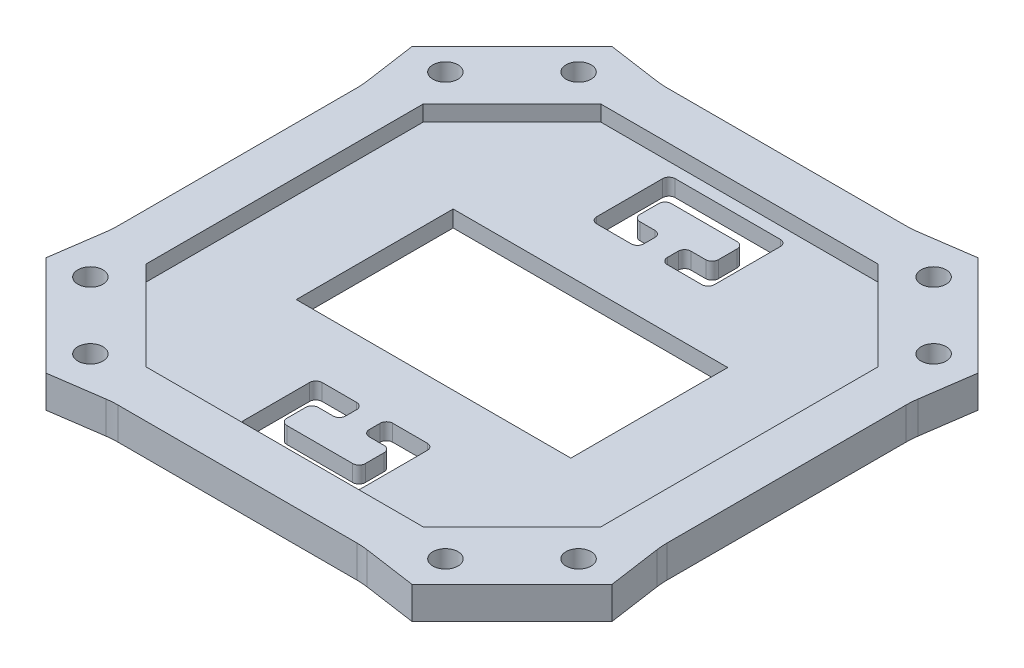
SolidWorks part; units mm, degrees
ref_plane "Front Plane" through (0, 0, 0) normal (0, 0, 1) x (1, 0, 0)
ref_plane "Top Plane" through (0, 0, 0) normal (0, 1, 0) x (1, 0, 0)
ref_plane "Right Plane" through (0, 0, 0) normal (1, 0, 0) x (0, 0, -1)
sketch "Sketch1" plane through (0, 0, 0) normal (0, 1, 0) x (1, 0, 0)
  line L0 (0, 0) -> (84.8528, 84.8528) construction
  line L5 (35, -35) -> (-35, 35) construction
  line L6 (35, 35) -> (-35, -35) construction
  line L7 (0, -62.8714) -> (0, 35) construction
  line L8 (15.934, 35) -> (-15.934, 35)
  line L9 (35, -15.934) -> (35, 15.934)
  line L10 (-15.934, -35) -> (15.934, -35)
  line L11 (-35, 15.934) -> (-35, -15.934)
  line L12 (20.5061, 33.234) -> (33.234, 20.5061) construction
  line L13 (36.0624, 23.3345) -> (23.3345, 36.0624)
  line L14 (15.934, 35) -> (23.3345, 36.0624)
  line L15 (35, 15.934) -> (36.0624, 23.3345)
  line L16 (15.934, -35) -> (23.3345, -36.0624)
  line L17 (23.3345, -36.0624) -> (36.0624, -23.3345)
  line L18 (35, -15.934) -> (36.0624, -23.3345)
  line L19 (-35, -15.934) -> (-36.0624, -23.3345)
  line L20 (-36.0624, -23.3345) -> (-23.3345, -36.0624)
  line L21 (-15.934, -35) -> (-23.3345, -36.0624)
  line L22 (-15.934, 35) -> (-23.3345, 36.0624)
  line L23 (-23.3345, 36.0624) -> (-36.0624, 23.3345)
  line L24 (-35, 15.934) -> (-36.0624, 23.3345)
  circle A0 centre (22.6274, 31.1127) radius 1.6
  circle A1 centre (31.1127, 22.6274) radius 1.6
  circle A2 centre (22.6274, -31.1127) radius 1.6
  circle A3 centre (31.1127, -22.6274) radius 1.6
  circle A4 centre (-31.1127, -22.6274) radius 1.6
  circle A5 centre (-22.6274, -31.1127) radius 1.6
  circle A6 centre (-22.6274, 31.1127) radius 1.6
  circle A7 centre (-31.1127, 22.6274) radius 1.6
  point P0 (0, 0)
  point P13 (0, 35)
  point P22 (0, 0)
  point P29 (29.6985, 29.6985)
  point P56 (0, 0)
  dimension "D10" = 3.2
  dimension "D11" = 3.2
  dimension "D12" = 6
  dimension "D13" = 6
  dimension "D1" = 70
  dimension "D2" = 70
  dimension "D3" = 120
  dimension "D5" = 18
  dimension "D6" = 9
  dimension "D7" = 82
  dimension "D8" = 18
  dimension "D9" = 4
  dimension "D4" = 4
  dimension "D14" = 4
extrude "Boss-Extrude1" add sketch "Sketch1" along normal blind 4.1
sketch "Sketch2" plane through (0, 4.1, 0) normal (0, 1, 0) x (1, 0, 0)
  line L0 (0, 35) -> (0, 0) construction
  line L1 (15.934, 35) -> (-15.934, 35) construction
  line L2 (0, 0) -> (-35, 0) construction
  line L3 (-35, 15.934) -> (-35, -15.934) construction
  line L4 (-17.669, 29) -> (17.669, 29)
  line L5 (17.669, 29) -> (29, 17.669)
  line L6 (29, 17.669) -> (29, -17.669)
  line L7 (29, -17.669) -> (17.669, -29)
  line L8 (17.669, -29) -> (-17.669, -29)
  line L9 (-17.669, -29) -> (-29, -17.669)
  line L10 (-29, -17.669) -> (-29, 17.669)
  line L11 (-29, 17.669) -> (-17.669, 29)
  line L12 (-15.934, -35) -> (15.934, -35) construction
  line L13 (-36.0624, -23.3345) -> (-23.3345, -36.0624) construction
  line L14 (23.3345, -36.0624) -> (36.0624, -23.3345) construction
  point P11 (0, 29)
  point P24 (23.3345, -23.3345)
  dimension "D1" = 6
  dimension "D2" = 6
  dimension "D3" = 9
  dimension "D4" = 9
extrude "Cut-Extrude1" cut sketch "Sketch2" against normal blind 2
sketch "Sketch3" plane through (0, 2.1, 0) normal (0, 1, 0) x (1, 0, 0)
  line L0 (0, 29) -> (0, 0) construction
  line L1 (17.669, 29) -> (-17.669, 29) construction
  line L2 (0, 0) -> (-29, 0) construction
  line L3 (-29, 17.669) -> (-29, -17.669) construction
  line L4 (-15, -4.5951) -> (-15, 4.5951)
  line L5 (-16.0792, 6.8995) -> (-24.0792, 13.5676)
  line L6 (-29, 11.2631) -> (-29, -11.2631)
  line L7 (-24.0792, -13.5676) -> (-16.0792, -6.8995)
  line L8 (-13.5676, 24.0792) -> (-6.8995, 16.0792)
  line L9 (11.2631, 29) -> (-11.2631, 29)
  line L10 (6.8995, 16.0792) -> (13.5676, 24.0792)
  line L11 (-4.5951, 15) -> (4.5951, 15)
  line L12 (24.0792, 13.5676) -> (16.0792, 6.8995)
  line L13 (29, -11.2631) -> (29, 11.2631)
  line L14 (16.0792, -6.8995) -> (24.0792, -13.5676)
  line L15 (15, 4.5951) -> (15, -4.5951)
  line L16 (13.5676, -24.0792) -> (6.8995, -16.0792)
  line L17 (-11.2631, -29) -> (11.2631, -29)
  line L18 (-6.8995, -16.0792) -> (-13.5676, -24.0792)
  line L19 (4.5951, -15) -> (-4.5951, -15)
  arc A0 (-15, 4.5951) -> (-16.0792, 6.8995) centre (-18, 4.5951) ccw
  arc A1 (-15, -4.5951) -> (-16.0792, -6.8995) centre (-18, -4.5951) cw
  arc A2 (-29, -11.2631) -> (-24.0792, -13.5676) centre (-26, -11.2631) ccw
  arc A3 (-24.0792, 13.5676) -> (-29, 11.2631) centre (-26, 11.2631) ccw
  arc A4 (-11.2631, 29) -> (-13.5676, 24.0792) centre (-11.2631, 26) ccw
  arc A5 (13.5676, 24.0792) -> (11.2631, 29) centre (11.2631, 26) ccw
  arc A6 (4.5951, 15) -> (6.8995, 16.0792) centre (4.5951, 18) ccw
  arc A7 (-4.5951, 15) -> (-6.8995, 16.0792) centre (-4.5951, 18) cw
  arc A8 (29, 11.2631) -> (24.0792, 13.5676) centre (26, 11.2631) ccw
  arc A9 (24.0792, -13.5676) -> (29, -11.2631) centre (26, -11.2631) ccw
  arc A10 (15, -4.5951) -> (16.0792, -6.8995) centre (18, -4.5951) ccw
  arc A11 (15, 4.5951) -> (16.0792, 6.8995) centre (18, 4.5951) cw
  arc A12 (11.2631, -29) -> (13.5676, -24.0792) centre (11.2631, -26) ccw
  arc A13 (-13.5676, -24.0792) -> (-11.2631, -29) centre (-11.2631, -26) ccw
  arc A14 (-4.5951, -15) -> (-6.8995, -16.0792) centre (-4.5951, -18) ccw
  arc A15 (4.5951, -15) -> (6.8995, -16.0792) centre (4.5951, -18) cw
  point P11 (-15, 0)
  point P17 (-15, 6)
  point P20 (-15, -6)
  point P23 (-29, -17.669)
  point P26 (-29, 17.669)
  point P66 (0, 0)
  dimension "D3" = 3
  dimension "D1" = 15
  dimension "D2" = 12
  dimension "D4" = 4
extrude "Cut-Extrude2" [suppressed] cut sketch "Sketch3" against normal blind 1.5
sketch "Sketch4" plane through (0, 2.1, 0) normal (0, 1, 0) x (1, 0, 0)
  line L1 (0, 0) -> (15.25, 0) construction
  line L2 (0, 0) -> (0, 15.25) construction
  line L3 (0, 15.25) -> (15.25, 15.25) construction
  line L4 (15.25, 0) -> (15.25, 15.25) construction
  circle A0 centre (15.25, 15.25) radius 1.5
  dimension "D2" = 3
  dimension "D1" = 15.25
extrude "Cut-Extrude3" [suppressed] cut sketch "Sketch4" against normal through all
sketch "Sketch5" [suppressed] plane through (0, 2, 0) normal (0, 1, 0) x (1, 0, 0)
  circle A0 centre (15.25, 15.25) radius 4
  circle A1 centre (15.25, 15.25) radius 1.5 construction
  circle A2 centre (15.25, 15.25) radius 1.5
  dimension "D1" = 8
extrude "Boss-Extrude4" [suppressed] add sketch "Sketch5" along normal blind 1.5
ref_axis "Axis1" [suppressed] through (0, -0.2, 0) along (0, 1, 0)
pattern_circular "CirPattern1" [suppressed] count 4 over 360 about axis through (0, -0.2, 0) along (0, 1, 0) of bodies 107
fillet "Fillet1" [suppressed] radius 2
fillet "Fillet2" radius 10 8 edges at (-15.934, 2.05, -35) (15.934, 2.05, -35) (35, 2.05, -15.934) (35, 2.05, 15.934) (-35, 2.05, -15.934) (-35, 2.05, 15.934) (15.934, 2.05, 35) (-15.934, 2.05, 35)
sketch "Sketch6" plane through (0, 2.1, 0) normal (0, 1, 0) x (1, 0, 0)
  line L0 (0, 29) -> (0, 0) construction
  line L1 (17.669, 29) -> (-17.669, 29) construction
  line L2 (0, 0) -> (-24.9179, 0) construction
  line L3 (-1.5, 19.7) -> (-1.5, 18.3)
  line L4 (-6.7, 27.5) -> (6.7, 27.5)
  line L5 (-7.5, 26.7) -> (-7.5, 18.3)
  line L6 (-6.7, 17.5) -> (-2.3, 17.5)
  line L7 (7.5, 26.7) -> (7.5, 18.3)
  line L8 (-7.5, 27.5) -> (7.5, 17.5) construction
  line L9 (-7.5, 17.5) -> (7.5, 27.5) construction
  line L10 (4.2, 20.5) -> (2.3, 20.5)
  line L11 (5, 21.3) -> (5, 23.7)
  line L12 (4.2, 24.5) -> (-4.2, 24.5)
  line L13 (-5, 21.3) -> (-5, 23.7)
  line L14 (5, 20.5) -> (-5, 24.5) construction
  line L15 (5, 24.5) -> (-5, 20.5) construction
  line L16 (1.5, 19.7) -> (1.5, 18.3)
  line L17 (-2.3, 20.5) -> (-4.2, 20.5)
  line L18 (2.3, 17.5) -> (6.7, 17.5)
  line L19 (5, -24.5) -> (-5, -20.5) construction
  line L20 (5, -20.5) -> (-5, -24.5) construction
  line L21 (-7.5, -17.5) -> (7.5, -27.5) construction
  line L22 (-7.5, -27.5) -> (7.5, -17.5) construction
  line L23 (2.3, -17.5) -> (6.7, -17.5)
  line L24 (-2.3, -20.5) -> (-4.2, -20.5)
  line L25 (1.5, -19.7) -> (1.5, -18.3)
  line L26 (-5, -21.3) -> (-5, -23.7)
  line L27 (4.2, -24.5) -> (-4.2, -24.5)
  line L28 (5, -21.3) -> (5, -23.7)
  line L29 (4.2, -20.5) -> (2.3, -20.5)
  line L30 (7.5, -26.7) -> (7.5, -18.3)
  line L31 (-6.7, -17.5) -> (-2.3, -17.5)
  line L32 (-7.5, -26.7) -> (-7.5, -18.3)
  line L33 (-6.7, -27.5) -> (6.7, -27.5)
  line L34 (-1.5, -19.7) -> (-1.5, -18.3)
  arc A0 (1.5, 18.3) -> (2.3, 17.5) centre (2.3, 18.3) ccw
  arc A1 (1.5, 19.7) -> (2.3, 20.5) centre (2.3, 19.7) cw
  arc A2 (-1.5, 18.3) -> (-2.3, 17.5) centre (-2.3, 18.3) cw
  arc A3 (-4.2, 20.5) -> (-5, 21.3) centre (-4.2, 21.3) cw
  arc A4 (5, 23.7) -> (4.2, 24.5) centre (4.2, 23.7) ccw
  arc A5 (4.2, 20.5) -> (5, 21.3) centre (4.2, 21.3) ccw
  arc A6 (-4.2, 24.5) -> (-5, 23.7) centre (-4.2, 23.7) ccw
  arc A7 (-1.5, 19.7) -> (-2.3, 20.5) centre (-2.3, 19.7) ccw
  arc A8 (6.7, 27.5) -> (7.5, 26.7) centre (6.7, 26.7) cw
  arc A9 (-7.5, 18.3) -> (-6.7, 17.5) centre (-6.7, 18.3) ccw
  arc A10 (-6.7, 27.5) -> (-7.5, 26.7) centre (-6.7, 26.7) ccw
  arc A11 (6.7, 17.5) -> (7.5, 18.3) centre (6.7, 18.3) ccw
  arc A12 (6.7, -17.5) -> (7.5, -18.3) centre (6.7, -18.3) cw
  arc A13 (-6.7, -27.5) -> (-7.5, -26.7) centre (-6.7, -26.7) cw
  arc A14 (-7.5, -18.3) -> (-6.7, -17.5) centre (-6.7, -18.3) cw
  arc A15 (6.7, -27.5) -> (7.5, -26.7) centre (6.7, -26.7) ccw
  arc A16 (-1.5, -19.7) -> (-2.3, -20.5) centre (-2.3, -19.7) cw
  arc A17 (-4.2, -24.5) -> (-5, -23.7) centre (-4.2, -23.7) cw
  arc A18 (4.2, -20.5) -> (5, -21.3) centre (4.2, -21.3) cw
  arc A19 (5, -23.7) -> (4.2, -24.5) centre (4.2, -23.7) cw
  arc A20 (-4.2, -20.5) -> (-5, -21.3) centre (-4.2, -21.3) ccw
  arc A21 (-1.5, -18.3) -> (-2.3, -17.5) centre (-2.3, -18.3) ccw
  arc A22 (1.5, -19.7) -> (2.3, -20.5) centre (2.3, -19.7) ccw
  arc A23 (1.5, -18.3) -> (2.3, -17.5) centre (2.3, -18.3) cw
  point P6 (0, 22.5)
  point P12 (0, 22.5)
  point P22 (1.5, 17.5)
  point P25 (1.5, 20.5)
  point P28 (-1.5, 17.5)
  point P43 (-1.5, 20.5)
  point P100 (-1.5, -20.5)
  point P101 (-1.5, -17.5)
  point P102 (1.5, -20.5)
  point P103 (1.5, -17.5)
  point P104 (0, -22.5)
  dimension "D7" = 0.8
  dimension "D1" = 17.5
  dimension "D2" = 15
  dimension "D3" = 10
  dimension "D4" = 2.5
  dimension "D5" = 3
  dimension "D6" = 6
extrude "Cut-Extrude4" cut sketch "Sketch6" against normal through all
sketch "Sketch7" plane through (0, 2.1, 0) normal (0, 1, 0) x (1, 0, 0)
  line L1 (17.5, -10) -> (-17.5, -10)
  line L2 (17.5, -10) -> (17.5, 10)
  line L3 (17.5, 10) -> (-17.5, 10)
  line L4 (-17.5, -10) -> (-17.5, 10)
  line L5 (17.5, -10) -> (-17.5, 10) construction
  line L6 (17.5, 10) -> (-17.5, -10) construction
  point P0 (0, 0)
  dimension "D1" = 35
  dimension "D2" = 20
extrude "Cut-Extrude5" cut sketch "Sketch7" against normal through all
